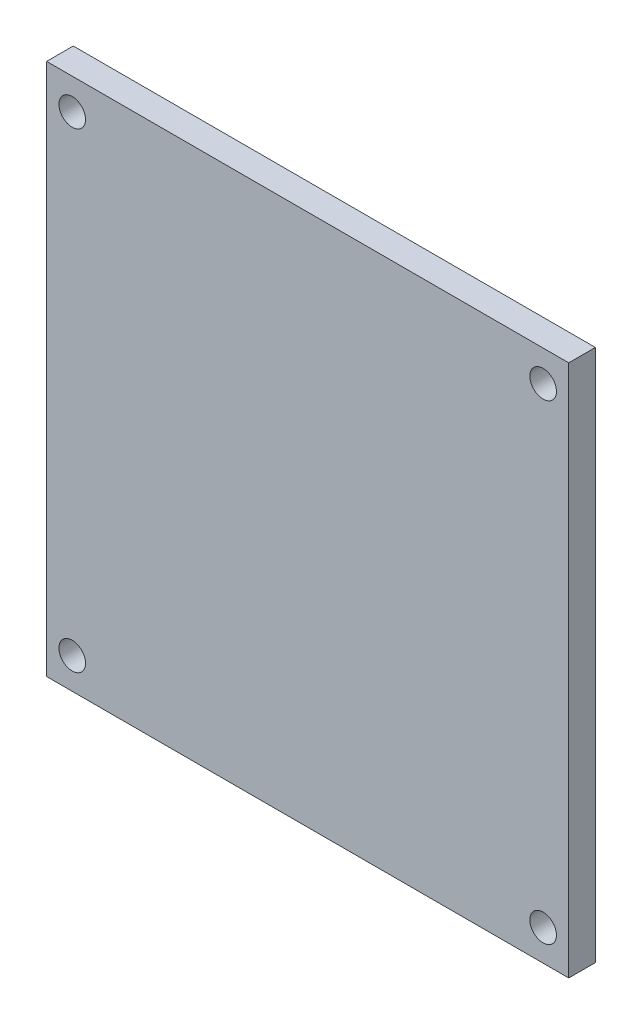
SolidWorks part; units mm, degrees
ref_plane "Front Plane" through (0, 0, 0) normal (0, 0, 1) x (1, 0, 0)
ref_plane "Top Plane" through (0, 0, 0) normal (0, 1, 0) x (1, 0, 0)
ref_plane "Right Plane" through (0, 0, 0) normal (1, 0, 0) x (0, 0, -1)
sketch "Sketch1" plane through (0, 0, 0) normal (0, 0, 1) x (1, 0, 0)
  line L1 (24.892, 25.4) -> (-24.892, 25.4)
  line L2 (24.892, 25.4) -> (24.892, -25.4)
  line L3 (24.892, -25.4) -> (-24.892, -25.4)
  line L4 (-24.892, 25.4) -> (-24.892, -25.4)
  line L5 (24.892, 25.4) -> (-24.892, -25.4) construction
  line L6 (24.892, -25.4) -> (-24.892, 25.4) construction
  point P0 (0, 0)
  dimension "D1" = 50.8
  dimension "D2" = 49.784
extrude "Boss-Extrude1" add sketch "Sketch1" along normal blind 2.54
sketch "Sketch2" plane through (0, 0, 2.54) normal (0, 0, 1) x (1, 0, 0)
  line L0 (0, -25.4) -> (0, 25.4) construction
  line L2 (-24.892, 0) -> (24.892, 0) construction
  line L3 (-22.479, 0) -> (-22.479, 22.479) construction
  line L4 (-24.892, 25.4) -> (-24.892, -25.4)
  line L5 (-24.892, -25.4) -> (24.892, -25.4)
  line L6 (24.892, -25.4) -> (24.892, 25.4)
  line L7 (24.892, 25.4) -> (-24.892, 25.4)
  line L8 (-24.892, 25.4) -> (-24.892, -25.4)
  line L9 (-24.892, -25.4) -> (24.892, -25.4)
  line L10 (24.892, -25.4) -> (24.892, 25.4)
  line L11 (24.892, 25.4) -> (-24.892, 25.4)
  circle A1 centre (-22.479, 22.479) radius 1.5875
  circle A3 centre (22.479, 22.479) radius 1.5875
  circle A5 centre (-22.479, -22.479) radius 1.5875
  circle A7 centre (22.479, -22.479) radius 1.5875
  dimension "D2" = 3.175
  dimension "D1" = 0
sketch "Sketch3" plane through (0, 0, 2.54) normal (0, 0, 1) x (1, 0, 0)
  circle A0 centre (22.4506, -22.4506) radius 1.27 construction
  circle A1 centre (22.4506, 22.4506) radius 1.27 construction
  circle A2 centre (-22.4506, -22.4506) radius 1.27 construction
  circle A3 centre (-22.4506, 22.4506) radius 1.27 construction
  circle A4 centre (22.4506, -22.4506) radius 1.27
  circle A5 centre (22.4506, 22.4506) radius 1.27
  circle A6 centre (-22.4506, -22.4506) radius 1.27
  circle A7 centre (-22.4506, 22.4506) radius 1.27
extrude "Cut-Extrude1" cut sketch "Sketch3" against normal through all
equation "\"HOLE SIZE\"= .125"
